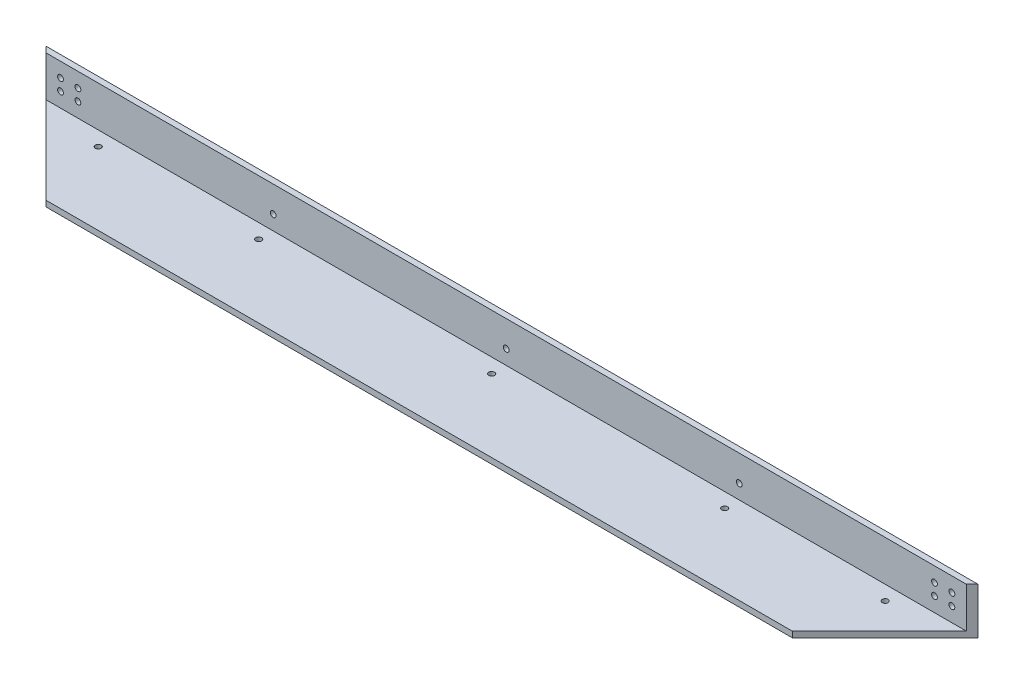
SolidWorks part; units mm, degrees
ref_plane "Front Plane" through (0, 0, 0) normal (0, 0, 1) x (1, 0, 0)
ref_plane "Top Plane" through (0, 0, 0) normal (0, 1, 0) x (1, 0, 0)
ref_plane "Right Plane" through (0, 0, 0) normal (1, 0, 0) x (0, 0, -1)
sketch "Sketch1" plane through (0, 0, 0) normal (1, 0, 0) x (0, 0, -1)
  line L0 (0, 0) -> (-50.8, 0)
  line L1 (-50.8, 0) -> (-50.8, 3.175)
  line L2 (-50.8, 3.175) -> (-3.175, 3.175)
  line L3 (-3.175, 3.175) -> (-3.175, 25.4)
  line L4 (-3.175, 25.4) -> (0, 25.4)
  line L5 (0, 25.4) -> (0, 0)
  dimension "LHeight" = 25.4
  dimension "LWidth" = 50.8
  dimension "LMaterialThickness" = 3.175
  dimension "D1" = 47.625
  dimension "D2" = 22.225
  dimension "D3" = 3.175
extrude "Boss-Extrude1" add sketch "Sketch1" along normal blind 510
chamfer "Chamfer6" distance 50.8 angle 45 1 edges at (510, 1.5875, 50.8)
chamfer "Chamfer7" distance 50.8 angle 45 1 edges at (0, 1.5875, 50.8)
sketch "FrontSideHoles-Sketch2" plane through (0, 0, 0) normal (0, 0, -1) x (-1, 0, 0)
  line L0 (0, 0) -> (0, 25.4) construction
  line L1 (-510, 0) -> (0, 0) construction
  line L2 (-510, 0) -> (-510, 25.4) construction
  circle A0 centre (-498.8875, 17.4625) radius 1.5875
  circle A1 centre (-489.3625, 17.4625) radius 1.5875
  circle A2 centre (-20.6375, 17.4625) radius 1.5875
  circle A3 centre (-11.1125, 17.4625) radius 1.5875
  circle A4 centre (-11.1125, 11.1125) radius 1.5875
  circle A5 centre (-20.6375, 11.1125) radius 1.5875
  circle A6 centre (-489.3625, 11.1125) radius 1.5875
  circle A7 centre (-498.8875, 11.1125) radius 1.5875
  circle A8 centre (-382.5, 11.1125) radius 1.5875
  circle A9 centre (-255, 11.1125) radius 1.5875
  circle A10 centre (-127.5, 11.1125) radius 1.5875
  dimension "D5" = 3.175
  dimension "D1" = 11.1125
  dimension "D2" = 20.6375
  dimension "D3" = 11.1125
  dimension "D4" = 20.6375
  dimension "D6" = 7.9375
  dimension "D7" = 11.1125
  dimension "D8" = 127.5
  dimension "D9" = 127.5
  dimension "D10" = 127.5
extrude "FrontSideHoles-Cut-Extrude2" cut sketch "FrontSideHoles-Sketch2" against normal through all
sketch "BottomHoles-Sketch2" plane through (0, 0, 0) normal (0, -1, 0) x (1, 0, 0)
  line L0 (510, 0) -> (0, 0) construction
  circle A0 centre (39.6875, 11.1125) radius 1.5875
  circle A1 centre (470.3125, 11.1125) radius 1.5875
  circle A2 centre (127.5, 11.1125) radius 1.5875
  circle A3 centre (255, 11.1125) radius 1.5875
  circle A4 centre (382.5, 11.1125) radius 1.5875
  dimension "D1" = 11.1125
  dimension "D4" = 3.175
  dimension "D2" = 39.6875
  dimension "D3" = 39.6875
  dimension "D5" = 127.5
  dimension "D6" = 127.5
  dimension "D7" = 127.5
extrude "BottomHoles-Cut-Extrude1" cut sketch "BottomHoles-Sketch2" against normal through all
equation "\"LowerRailWidth\"= 2.00in"
equation "\"LowerRailHeight\"= 1.00in"
equation "\"RailThickness\"= .125in'Spec"
equation "\"SideRailHoleX1FromSide\"= \"HoleOffsetFromSide\""
equation "\"SideRailHoleX2FromSide\"= \"VSWidth\" - \"HoleOffsetFromEdge\" - \"RailThickness\"'Equals 20.6375"
equation "\"SideRailHoleY1FromEdge\"= \"HoleOffsetFromEdge\""
equation "\"FrontBackRailLength\"= 510mm"
equation "\"VSWidth\"= 1.25in'Spec"
equation "\"HoleOffsetFromEdge\"= \"RailThickness\" * 2.5"
equation "\"HoleOffsetFromSide\"= \"RailThickness\" * 3.5"
equation "\"SideRailHoleY2FromSide\"= \"HoleOffsetFromSide\""
equation "\"FasteningHoleDiameter\"= .125in"
equation "\"D1@Boss-Extrude1\"=\"FrontBackRailLength\""
equation "\"D1@Chamfer6\"=\"LowerRailWidth\""
equation "\"D1@Chamfer7\"=\"LowerRailWidth\""
equation "\"D1@FrontSideHoles-Sketch2\" = \"SideRailHoleX1FromSide\""
equation "\"D2@FrontSideHoles-Sketch2\" = \"SideRailHoleX2FromSide\""
equation "\"D3@FrontSideHoles-Sketch2\" = \"SideRailHoleX1FromSide\""
equation "\"D4@FrontSideHoles-Sketch2\" = \"SideRailHoleX2FromSide\""
equation "\"D5@FrontSideHoles-Sketch2\" = \"FasteningHoleDiameter\""
equation "\"D6@FrontSideHoles-Sketch2\" = \"SideRailHoleY1FromEdge\""
equation "\"D7@FrontSideHoles-Sketch2\" = \"SideRailHoleY2FromSide\""
equation "\"LHeight@Sketch1\"=\"LowerRailHeight\""
equation "\"LWidth@Sketch1\"=\"LowerRailWidth\""
equation "\"LowerCornerBlockWidth\"= \"LowerRailWidth\" - \"RailThickness\" * 2'Room for left front stepper"
equation "\"D1@BottomHoles-Sketch2\"=\"LowerCornerBlockY1FromSide\""
equation "\"D2@BottomHoles-Sketch2\"=\"LowerCornerBlockX1FromSide\""
equation "\"D3@BottomHoles-Sketch2\"=\"LowerCornerBlockX1FromSide\""
equation "\"D4@BottomHoles-Sketch2\" = \"FasteningHoleDiameter\""
equation "\"LowerCornerBlockX1FromSide\"= \"LowerCornerBlockWidth\" - \"HoleOffsetFromEdge\" + \"RailThickness\""
equation "\"LowerCornerBlockY1FromSide\"= \"HoleOffsetFromSide\""
equation "\"FrontOrBackEnclosureOffsets\"= \"FrontBackRailLength\" / 4"
equation "\"D5@BottomHoles-Sketch2\"=\"FrontOrBackEnclosureOffsets\""
equation "\"D6@BottomHoles-Sketch2\"=\"FrontOrBackEnclosureOffsets\""
equation "\"D7@BottomHoles-Sketch2\"=\"FrontOrBackEnclosureOffsets\""
equation "\"D8@FrontSideHoles-Sketch2\"=\"FrontOrBackEnclosureOffsets\""
equation "\"D9@FrontSideHoles-Sketch2\"=\"FrontOrBackEnclosureOffsets\""
equation "\"D10@FrontSideHoles-Sketch2\"=\"FrontOrBackEnclosureOffsets\""
